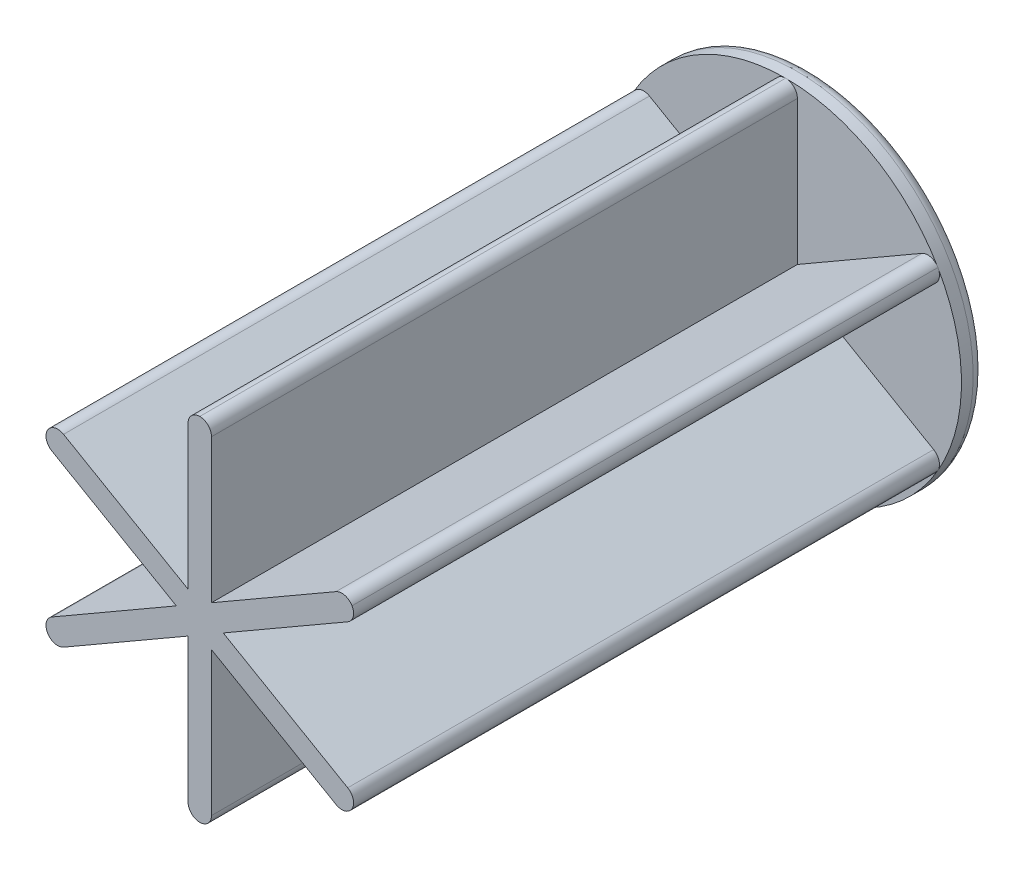
SolidWorks part; units mm, degrees
ref_plane "Front Plane" through (0, 0, 0) normal (0, 0, 1) x (1, 0, 0)
ref_plane "Top Plane" through (0, 0, 0) normal (0, 1, 0) x (1, 0, 0)
ref_plane "Right Plane" through (0, 0, 0) normal (1, 0, 0) x (0, 0, -1)
sketch "Sketch1" plane through (0, 0, 0) normal (0, 0, 1) x (1, 0, 0)
  circle A0 centre (0, 0) radius 15
  dimension "D1" = 30
extrude "Boss-Extrude1" add sketch "Sketch1" along normal blind 2
sketch "Sketch2" plane through (0, 0, 2) normal (0, 0, 1) x (1, 0, 0)
  line L2 (-1, -14.9666) -> (-1, 14.9666)
  line L4 (1, -14.9666) -> (1, 14.9666)
  line L5 (-1, -14.9666) -> (1, 14.9666) construction
  line L6 (-1, 14.9666) -> (1, -14.9666) construction
  arc A0 (1, 14.9666) -> (-1, 14.9666) centre (0, 0) ccw
  arc A2 (-1, -14.9666) -> (1, -14.9666) centre (0, 0) ccw
  dimension "D1" = 2
extrude "Boss-Extrude2" add sketch "Sketch2" along normal blind 50
pattern_circular "CirPattern1" count 3 every 60 about axis through (0, 0, 0) along (0, 0, 1) of "Boss-Extrude2"
sketch "Sketch3" plane through (0, 0, 0) normal (0, 0, -1) x (-1, 0, 0)
  line L0 (-2.5981, 1.5) -> (2.5981, 1.5)
  arc A0 (-2.5981, 1.5) -> (2.5981, 1.5) centre (0, 0) ccw
  dimension "D1" = 6
  dimension "D2" = 1.5
extrude "Cut-Extrude1" cut sketch "Sketch3" against normal blind 10
sketch "Sketch4" plane through (0, 0, 52) normal (0, 0, 1) x (1, 0, 0)
  circle A0 centre (0, 0) radius 15
  arc A1 (12.4615, 8.3493) -> (1, 14.9666) centre (0, 0) ccw construction
fillet "Fillet2" radius 1 18 edges at (0, -15, 52) (-12.9904, 7.5, 52) (-12.9904, -7.5, 52) (12.9904, -7.5, 52) (12.9904, 7.5, 52) (12.4615, 8.3493, 27) (-12.4615, -8.3493, 27) (-13.4615, 6.6173, 27) (13.4615, -6.6173, 27) (-12.4615, 8.3493, 27) (12.4615, -8.3493, 27) (13.4615, 6.6173, 27) (-13.4615, -6.6173, 27) (1, 14.9666, 27) (-1, 14.9666, 27) (-1, -14.9666, 27) (1, -14.9666, 27) (0, 15, 52)
fillet "Fillet3" radius 1 1 edges at (15, 0, 0)
